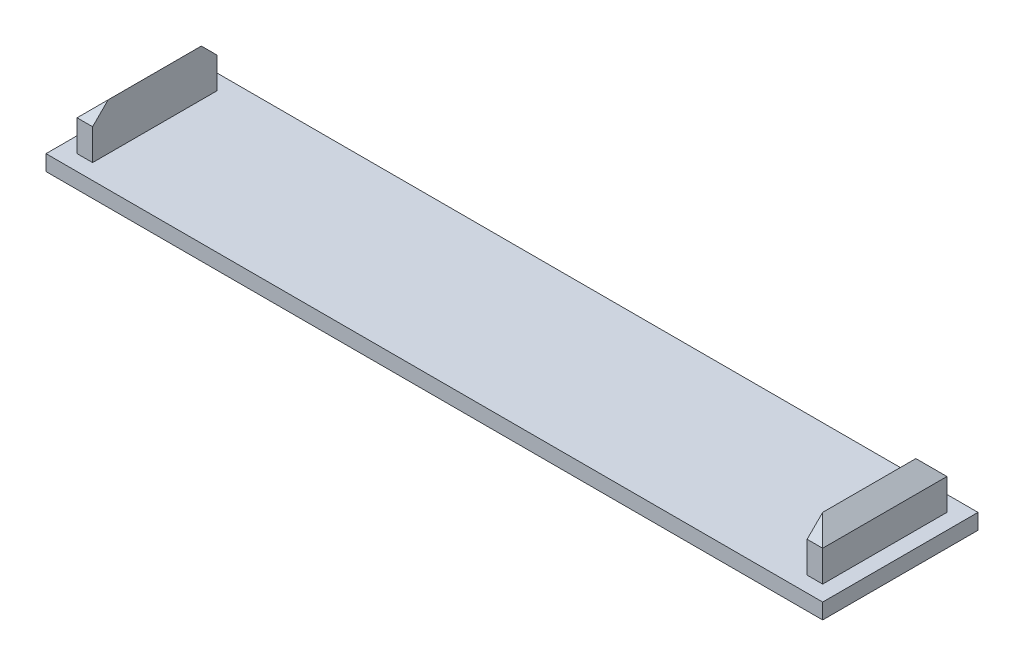
SolidWorks part; units mm, degrees
ref_plane "Front Plane" through (0, 0, 0) normal (0, 0, 1) x (1, 0, 0)
ref_plane "Top Plane" through (0, 0, 0) normal (0, 1, 0) x (1, 0, 0)
ref_plane "Right Plane" through (0, 0, 0) normal (1, 0, 0) x (0, 0, -1)
sketch "Sketch1" plane through (0, 0, 0) normal (0, 1, 0) x (1, 0, 0)
  line L1 (0, 0) -> (50, 0)
  line L2 (0, 0) -> (0, 10)
  line L3 (0, 10) -> (50, 10)
  line L4 (50, 0) -> (50, 10)
  dimension "D1" = 50
  dimension "D2" = 10
extrude "Boss-Extrude1" add sketch "Sketch1" along normal blind 1
sketch "Sketch2" plane through (0, 1, 0) normal (0, 1, 0) x (1, 0, 0)
  line L0 (0, 0) -> (50, 0) construction
  line L1 (1, 9) -> (2, 9)
  line L2 (1, 9) -> (1, 1)
  line L3 (1, 1) -> (2, 1)
  line L4 (2, 9) -> (2, 1)
  line L5 (0, 10) -> (0, 0) construction
  dimension "D1" = 1
  dimension "D2" = 8
  dimension "D3" = 1
  dimension "D4" = 1
extrude "Boss-Extrude2" add sketch "Sketch2" along normal blind 3
chamfer "Chamfer1" distance 1 angle 45 3 edges at (1, 4, -5) (1.5, 4, -9) (1.5, 4, -1)
ref_plane "Plane1" through (25, 0, 0) normal (1, 0, 0) x (0, 0, -1)
mirror "Mirror1" about plane through (25, 0, 0) normal (1, 0, 0) of "Boss-Extrude2", "Chamfer1"
sketch "Sketch5" plane through (0, 0, 0) normal (0, -1, 0) x (1, 0, 0)
  line L0 (0, -10) -> (0, 0) construction
  line L1 (0, 0) -> (50, 0) construction
  text T0 "COMPRESSION TESTER CONNECTION" font "Century Gothic" height 2
  dimension "D1" = 0.75
  dimension "D2" = 6
extrude "Cut-Extrude1" cut sketch "Sketch5" against normal blind 0.2
